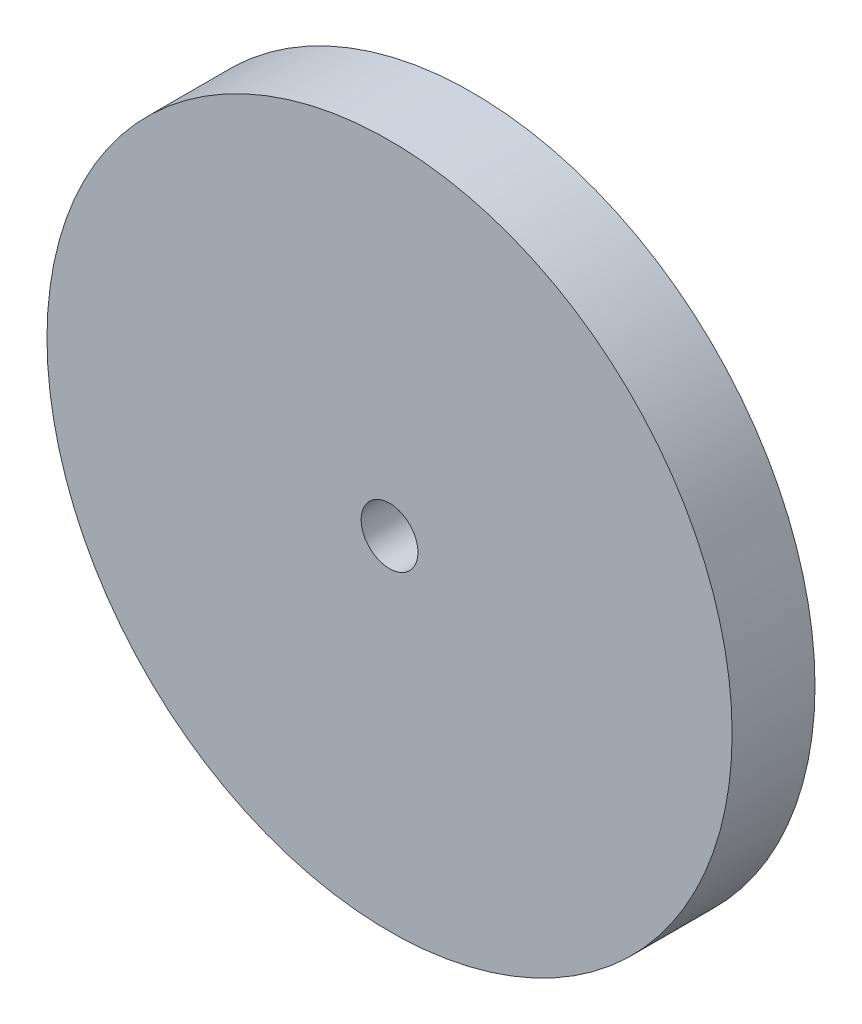
SolidWorks part; units mm, degrees
ref_plane "Front Plane" through (0, 0, 0) normal (0, 0, 1) x (1, 0, 0)
ref_plane "Top Plane" through (0, 0, 0) normal (0, 1, 0) x (1, 0, 0)
ref_plane "Right Plane" through (0, 0, 0) normal (1, 0, 0) x (0, 0, -1)
sketch "Sketch1" plane through (0, 0, 4.7625) normal (0, 0, 1) x (1, 0, 0)
  circle A1 centre (-44.6986, 0) radius 24.145
  circle A2 centre (-44.6986, 0) radius 2
  circle A3 centre (-44.6986, 0) radius 24.145 construction
  dimension "D1" = 4
extrude "Boss-Extrude1" add sketch "Sketch1" along normal blind 5.842
